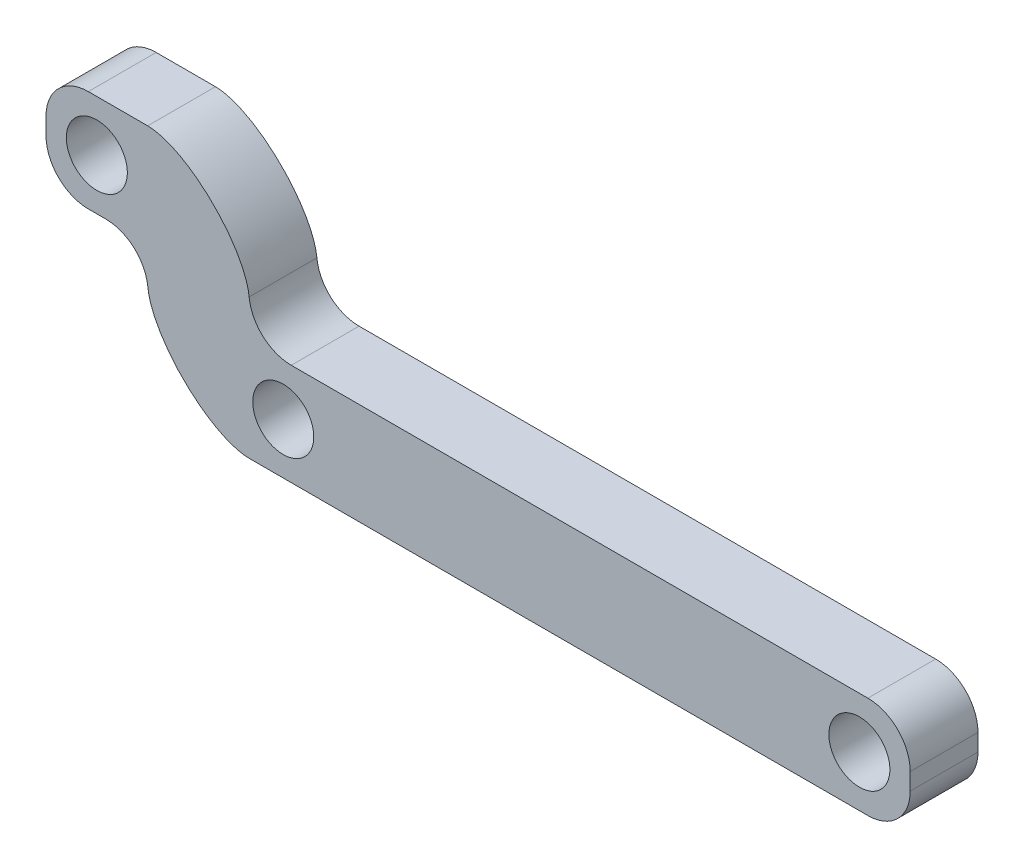
SolidWorks part; units mm, degrees
ref_plane "Front" through (0, 0, 0) normal (0, 0, 1) x (1, 0, 0)
ref_plane "Top" through (0, 0, 0) normal (0, 1, 0) x (1, 0, 0)
ref_plane "Right" through (0, 0, 0) normal (1, 0, 0) x (0, 0, -1)
sketch "Sketch1" plane through (0, 0, 0) normal (0, 0, 1) x (1, 0, 0)
  line L1 (0, 0) -> (-45, 0)
  line L2 (0, 0) -> (0, -6)
  line L3 (0, -6) -> (-45, -6)
  line L4 (-45, 0) -> (-45, -6)
  line L5 (-45, 0) -> (-39, 0)
  line L6 (-45, 0) -> (-45, 8)
  line L7 (-45, 8) -> (-39, 8)
  line L8 (-39, 0) -> (-39, 8)
  line L9 (-45, 8) -> (-51, 8)
  line L10 (-45, 8) -> (-45, 2)
  line L11 (-45, 2) -> (-51, 2)
  line L12 (-51, 8) -> (-51, 2)
  dimension "D1" = 6
  dimension "D2" = 45
  dimension "D3" = 6
  dimension "D4" = 8
  dimension "D5" = 6
  dimension "D6" = 6
extrude "Boss-Extrude1" add sketch "Sketch1" along normal blind 4 contours L1 L4 L3 L2 | L1 L8 L7 L6 | L9 L12 L11 L6 region at (-22.5, -3, 0) region at (-42, 4, 0) region at (-48, 5, 0)
sketch "Sketch2" plane through (0, 0, 0) normal (0, 0, -1) x (-1, 0, 0)
  line L0 (51, 8) -> (39, 8) construction
  line L1 (0, 0) -> (0, -6) construction
  line L2 (51, 8) -> (51, 2) construction
  circle A0 centre (3, -3) radius 1.8
  circle A1 centre (37, -3) radius 1.8
  circle A2 centre (48, 5) radius 1.8
  dimension "D1" = 3.6
  dimension "D2" = 3.6
  dimension "D3" = 3.6
  dimension "D4" = 3
  dimension "D5" = 3
  dimension "D6" = 34
  dimension "D7" = 3
extrude "Cut-Extrude1" cut sketch "Sketch2" against normal through all
fillet "Fillet2" radius 6 2 edges at (-45, -6, 2) (-39, 8, 2) conic rho 0.3
fillet "Fillet3" radius 2.5 6 edges at (-51, 8, 2) (-51, 2, 2) (-45, 2, 2) (-39, 0, 2) (0, 0, 2) (0, -6, 2)
equation "\"滑动-垂直孔\" = 0.6"
equation "\"滑动-水平孔\"= 0.3"
equation "\"松动-垂直孔\" = 0.3"
equation "\"松动-水平孔\"= 0.1"
equation "\"正常-垂直孔\" = 0.15"
equation "\"正常-水平孔\"= 0"
equation "\"紧缩-垂直孔\"= 0"
equation "\"紧缩-水平孔\"= - 0.1"
equation "\"D1@Sketch2\"=\"滑动-垂直孔\"+3"
equation "\"D2@Sketch2\"=\"滑动-垂直孔\"+3"
equation "\"D3@Sketch2\"=\"滑动-垂直孔\"+3"
